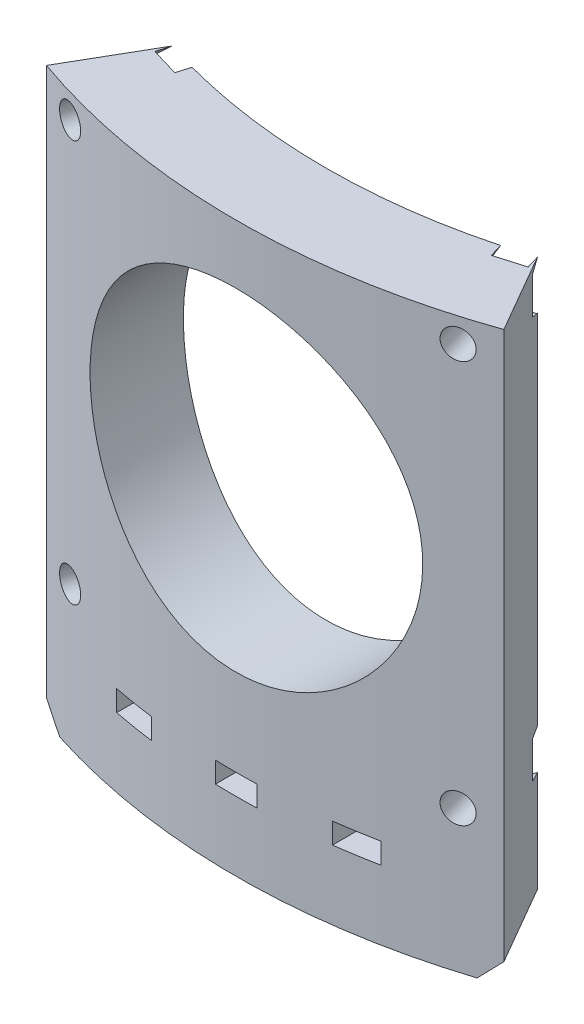
SolidWorks part; units mm, degrees
ref_plane "Спереди" through (0, 0, 0) normal (0, 0, 1) x (1, 0, 0)
ref_plane "Сверху" through (0, 0, 0) normal (0, 1, 0) x (1, 0, 0)
ref_plane "Справа" through (0, 0, 0) normal (1, 0, 0) x (0, 0, -1)
sketch "Эскиз1" plane through (0, 0, 0) normal (0, 1, 0) x (-1, 0, 0)
  line L0 (33, 7.3381) -> (26.3713, -4.1431)
  line L1 (-33, 7.3381) -> (-26.3713, -4.1431)
  line L2 (0, 13) -> (0, 0) construction
  line L3 (0, -86) -> (0, 0) construction
  arc A0 (-33, 7.3381) -> (33, 7.3381) centre (0, -86) cw
  arc A2 (-26.3713, -4.1431) -> (26.3713, -4.1431) centre (0, -86) cw
  dimension "D3" = 86
  dimension "D4" = 99
  dimension "D1" = 66
  dimension "D2" = 30
  dimension "D5" = 30
  dimension "D6" = 13
extrude "Бобышка-Вытянуть1" add sketch "Эскиз1" along normal blind 82
sketch "Эскиз2" plane through (0, 0, 0) normal (0, -1, 0) x (1, 0, 0)
  line L0 (0, -86) -> (0, 6.5) construction
  line L1 (0, 13) -> (0, 0) construction
  line L2 (-33, 7.3381) -> (-26.3713, -4.1431) construction
  line L3 (33, 7.3381) -> (26.3713, -4.1431) construction
  line L4 (-16.0609, 5.0857) -> (0, -86) construction
  line L5 (0, -86) -> (16.0609, 5.0857) construction
  arc A0 (-29.6857, 1.5975) -> (29.6857, 1.5975) centre (0, -86) cw construction
  circle A1 centre (0, 6.5) radius 1.75
  circle A2 centre (16.0609, 5.0857) radius 1.75
  circle A3 centre (-16.0609, 5.0857) radius 1.75
  dimension "D3" = 3.5
  dimension "D4" = 3.5
  dimension "D5" = 3.5
  dimension "D1" = 10
  dimension "D2" = 10
extrude "Вырез-Вытянуть1" cut sketch "Эскиз2" against normal blind 20
ref_plane "Плоскость1" through (0, 0, 13) normal (0, 0, 1) x (1, 0, 0)
sketch "Эскиз3" plane through (0, 0, 13) normal (0, 0, 1) x (1, 0, 0)
  line L0 (-16.0609, 0) -> (-16.0609, 11.5) construction
  line L1 (-16.0609, 11.5) -> (16.0609, 11.5) construction
  line L2 (16.0609, 11.5) -> (16.0609, 0) construction
  line L3 (0, 0) -> (0, 11.5) construction
  line L4 (33, 0) -> (-33, 0) construction
  line L5 (-17.8109, 0) -> (-14.3109, 0) construction
  line L6 (-19.0609, 13) -> (-13.0609, 13)
  line L7 (-19.0609, 13) -> (-19.0609, 10)
  line L8 (-19.0609, 10) -> (-13.0609, 10)
  line L9 (-13.0609, 13) -> (-13.0609, 10)
  line L10 (-19.0609, 13) -> (-13.0609, 10) construction
  line L11 (-19.0609, 10) -> (-13.0609, 13) construction
  line L12 (-3, 13) -> (3, 13)
  line L13 (-3, 13) -> (-3, 10)
  line L14 (-3, 10) -> (3, 10)
  line L15 (3, 13) -> (3, 10)
  line L16 (-3, 13) -> (3, 10) construction
  line L17 (-3, 10) -> (3, 13) construction
  line L18 (13.0609, 13) -> (19.0609, 13)
  line L19 (13.0609, 13) -> (13.0609, 10)
  line L20 (13.0609, 10) -> (19.0609, 10)
  line L21 (19.0609, 13) -> (19.0609, 10)
  line L22 (13.0609, 13) -> (19.0609, 10) construction
  line L23 (13.0609, 10) -> (19.0609, 13) construction
  line L24 (14.3109, 0) -> (17.8109, 0) construction
  dimension "D1" = 11.5
  dimension "D2" = 6
  dimension "D3" = 6
  dimension "D4" = 6
  dimension "D5" = 3
  dimension "D6" = 3
  dimension "D7" = 3
extrude "Вырез-Вытянуть2" cut sketch "Эскиз3" against normal through all
sketch "Эскиз4" plane through (0, 0, 13) normal (0, 0, 1) x (1, 0, 0)
  line L0 (0, 49.5) -> (0, 0) construction
  circle A0 centre (0, 49.5) radius 24
  dimension "D1" = 48
  dimension "D2" = 49.5
extrude "Вырез-Вытянуть3" cut sketch "Эскиз4" against normal through all
sketch "Эскиз5" plane through (0, 82, 0) normal (0, 1, 0) x (1, 0, 0)
  line L0 (16.6948, -11.5822) -> (0, 41.3669) construction
  line L1 (0, 41.3669) -> (0, 0) construction
  line L2 (0, 41.3669) -> (-16.6948, -11.5822) construction
  arc A0 (-33, -7.3381) -> (33, -7.3381) centre (0, 86) ccw construction
  arc A1 (-26.3713, 4.1431) -> (26.3713, 4.1431) centre (0, 86) ccw construction
  dimension "D1" = 35
  dimension "D2" = 17.5
ref_plane "Плоскость4" through (0, 0, 13) normal (0, 0, 1) x (1, 0, 0)
sketch "Эскиз7" plane through (0, 0, 13) normal (0, 0, 1) x (1, 0, 0)
  line L1 (-28, 77.5) -> (28, 77.5) construction
  line L2 (-28, 77.5) -> (-28, 21.5) construction
  line L3 (-28, 21.5) -> (28, 21.5) construction
  line L4 (28, 77.5) -> (28, 21.5) construction
  line L5 (-28, 77.5) -> (28, 21.5) construction
  line L6 (-28, 21.5) -> (28, 77.5) construction
  circle A0 centre (-28, 77.5) radius 1.75
  circle A1 centre (28, 77.5) radius 1.75
  circle A2 centre (28, 21.5) radius 1.75
  circle A3 centre (-28, 21.5) radius 1.75
  point P0 (0, 49.5)
  dimension "D3" = 3.5
  dimension "D4" = 3.5
  dimension "D5" = 3.5
  dimension "D6" = 3.5
  dimension "D1" = 56
  dimension "D2" = 56
extrude "Вырез-Вытянуть4" [suppressed] cut sketch "Эскиз7" against normal through all
sketch "Эскиз8" plane through (0, 0, 13) normal (0, 0, 1) x (1, 0, 0)
  line L0 (0, 73.5) -> (0, 25.5)
  line L1 (0, 25.5) -> (-24, 49.5)
  line L2 (-24, 49.5) -> (24, 49.5)
  circle A0 centre (0, 49.5) radius 24 construction
  point P8 (0, 49.5)
chamfer "Фаска1" distance 3 angle 45 2 edges at (29.6857, 0, 1.5975) (-29.6857, 0, 1.5975)
sketch "Эскиз9" plane through (0, 82, 0) normal (0, 1, 0) x (1, 0, 0)
  line L0 (-28, -8.9579) -> (-28, -13) construction
  line L1 (28, -8.9579) -> (28, -13) construction
  arc A0 (-33, -7.3381) -> (33, -7.3381) centre (0, 86) ccw construction
  point P0 (-28, -8.9579)
  point P1 (28, -8.9579)
ref_plane "Плоскость5" through (-28, 82, 8.9579) normal (-0.2828, 0, 0.9592) x (0.9592, 0, 0.2828)
ref_plane "Плоскость6" through (28, 82, 8.9579) normal (0.2828, 0, 0.9592) x (0.9592, 0, -0.2828)
sketch "Эскиз12" plane through (0, 82, 0) normal (0, 1, 0) x (1, 0, 0)
  line L0 (-28, -8.9579) -> (28, -8.9579) construction
  arc A0 (-33, -7.3381) -> (33, -7.3381) centre (0, 86) ccw construction
  point P6 (-28, -8.9579)
  point P7 (28, -8.9579)
  dimension "D1" = 56
sketch "Эскиз10" plane through (-28, 82, 8.9579) normal (-0.2828, 0, 0.9592) x (0.9592, 0, 0.2828)
  line L1 (4.9799, -32.5) -> (51.0201, -32.5) construction
  line L3 (0, 0) -> (0, -3.5) construction
  line L4 (0, -3.5) -> (0, -61.5) construction
  circle A0 centre (0, -3.5) radius 2.25
  circle A1 centre (0, -61.5) radius 2.25
  dimension "D3" = 4.5
  dimension "D6" = 4.5
  dimension "D2" = 29
  dimension "D4" = 29
extrude "Вырез-Вытянуть5" cut sketch "Эскиз10" against normal through all
sketch "Эскиз11" plane through (28, 82, 8.9579) normal (0.2828, 0, 0.9592) x (0.9592, 0, -0.2828)
  line L2 (0, 0) -> (0, -3.5) construction
  line L3 (0, -3.5) -> (0, -61.5) construction
  line L4 (-51.0201, -32.5) -> (-4.9799, -32.5) construction
  circle A0 centre (0, -3.5) radius 2.1
  circle A1 centre (0, -61.5) radius 2.1
  dimension "D3" = 4.2
  dimension "D4" = 4.2
  dimension "D1" = 29
  dimension "D2" = 29
extrude "Вырез-Вытянуть6" cut sketch "Эскиз11" against normal through all
ref_plane "Плоскость7" through (0.9856, 0, 3.3423) normal (0.2828, 0, 0.9592) x (0.9592, 0, -0.2828)
ref_plane "Плоскость8" through (-0.9856, 0, 3.3423) normal (-0.2828, 0, 0.9592) x (0.9592, 0, 0.2828)
sketch "Эскиз13" plane through (-0.9856, 0, 3.3423) normal (-0.2828, 0, 0.9592) x (0.9592, 0, 0.2828)
  line L1 (-24.3232, 24.6569) -> (-27.9232, 22.5785)
  line L2 (-27.9232, 22.5785) -> (-27.9232, 18.4215)
  line L3 (-27.9232, 18.4215) -> (-24.3232, 16.3431)
  line L4 (-24.3232, 16.3431) -> (-20.7232, 18.4215)
  line L5 (-20.7232, 18.4215) -> (-20.7232, 22.5785)
  line L6 (-20.7232, 22.5785) -> (-24.3232, 24.6569)
  line L7 (-22.2448, 74.9) -> (-20.1663, 78.5)
  line L8 (-20.1663, 78.5) -> (-22.2448, 82.1)
  line L9 (-22.2448, 82.1) -> (-26.4017, 82.1)
  line L10 (-26.4017, 82.1) -> (-28.4802, 78.5)
  line L11 (-28.4802, 78.5) -> (-26.4017, 74.9)
  line L12 (-26.4017, 74.9) -> (-22.2448, 74.9)
  circle A0 centre (-24.3232, 20.5) radius 3.6 construction
  circle A1 centre (-24.3232, 78.5) radius 3.6 construction
  dimension "D1" = 7.2
  dimension "D2" = 7.2
extrude "Вырез-Вытянуть7" cut sketch "Эскиз13" along normal blind 2 and the other way blind 2
sketch "Эскиз14" plane through (0.9856, 0, 3.3423) normal (0.2828, 0, 0.9592) x (0.9592, 0, -0.2828)
  line L1 (28.4802, 78.5) -> (26.4017, 82.1)
  line L2 (26.4017, 82.1) -> (22.2448, 82.1)
  line L3 (22.2448, 82.1) -> (20.1663, 78.5)
  line L4 (20.1663, 78.5) -> (22.2448, 74.9)
  line L5 (22.2448, 74.9) -> (26.4017, 74.9)
  line L6 (26.4017, 74.9) -> (28.4802, 78.5)
  line L7 (24.3232, 24.6569) -> (20.7232, 22.5785)
  line L8 (20.7232, 22.5785) -> (20.7232, 18.4215)
  line L9 (20.7232, 18.4215) -> (24.3232, 16.3431)
  line L10 (24.3232, 16.3431) -> (27.9232, 18.4215)
  line L11 (27.9232, 18.4215) -> (27.9232, 22.5785)
  line L12 (27.9232, 22.5785) -> (24.3232, 24.6569)
  circle A0 centre (24.3232, 78.5) radius 3.6 construction
  circle A1 centre (24.3232, 20.5) radius 3.6 construction
  dimension "D1" = 7.2
  dimension "D2" = 7.2
extrude "Вырез-Вытянуть8" cut sketch "Эскиз14" against normal blind 2 and the other way blind 2
